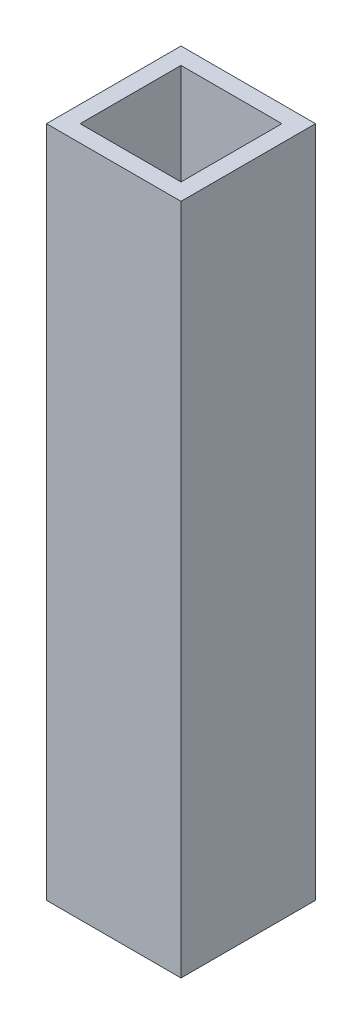
SolidWorks part; units mm, degrees
material "6061-T6 (SS)"
ref_plane "Front" through (0, 0, 0) normal (0, 0, 1) x (1, 0, 0)
ref_plane "Top" through (0, 0, 0) normal (0, 1, 0) x (1, 0, 0)
ref_plane "Right" through (0, 0, 0) normal (1, 0, 0) x (0, 0, -1)
sketch "Sketch1" plane through (0, 0, 0) normal (0, 1, 0) x (1, 0, 0)
  line L1 (-12.7, -12.7) -> (12.7, -12.7)
  line L2 (-12.7, -12.7) -> (-12.7, 12.7)
  line L3 (-12.7, 12.7) -> (12.7, 12.7)
  line L4 (12.7, -12.7) -> (12.7, 12.7)
  line L5 (-12.7, -12.7) -> (12.7, 12.7) construction
  line L6 (-12.7, 12.7) -> (12.7, -12.7) construction
  point P0 (0, 0)
  dimension "D1" = 25.4
extrude "Extrude-Thin1" add sketch "Sketch1" along normal blind 127 thin thin type one direction reverse wall 3.175
